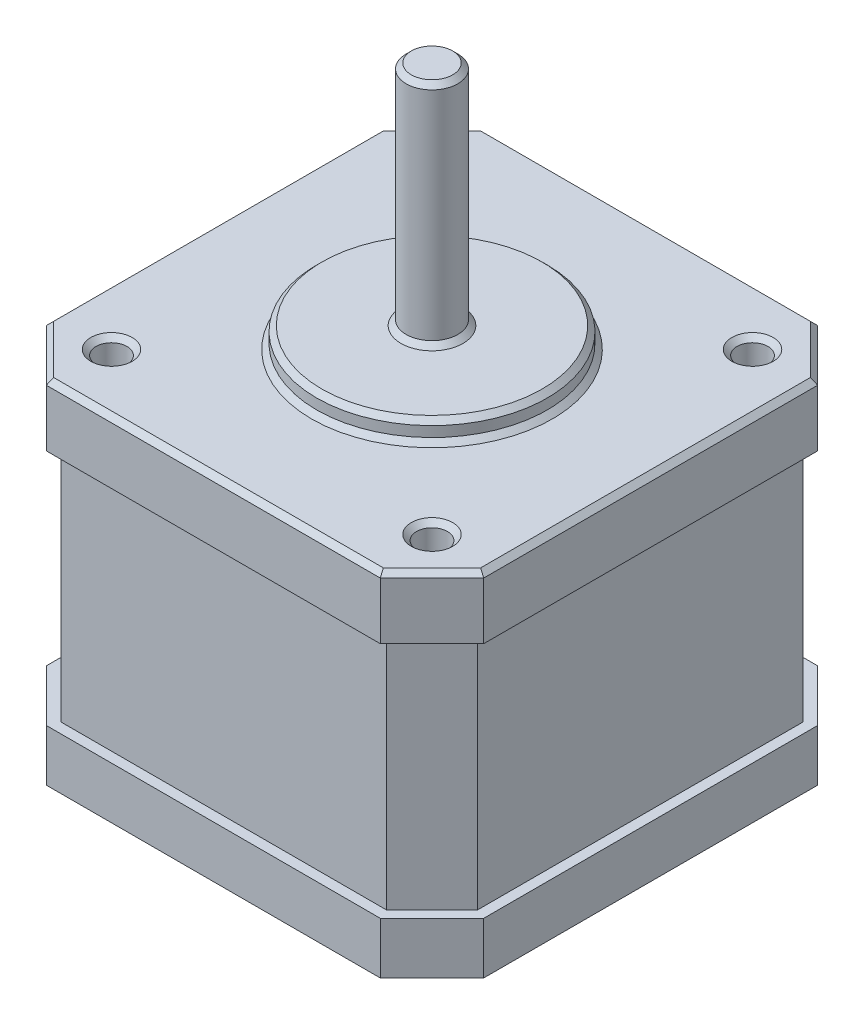
SolidWorks part; units mm, degrees
ref_plane "정면" through (0, 0, 0) normal (0, 0, 1) x (1, 0, 0)
ref_plane "윗면" through (0, 0, 0) normal (0, 1, 0) x (1, 0, 0)
ref_plane "우측면" through (0, 0, 0) normal (1, 0, 0) x (0, 0, -1)
sketch "스케치1" plane through (0, 0, 0) normal (0, 1, 0) x (1, 0, 0)
  line L0 (-21.15, 16.15) -> (-16.15, 21.15)
  line L1 (-16.15, -21.15) -> (16.15, -21.15)
  line L2 (-21.15, -16.15) -> (-21.15, 16.15)
  line L3 (-16.15, 21.15) -> (16.15, 21.15)
  line L4 (21.15, -16.15) -> (21.15, 16.15)
  line L5 (-21.15, -21.15) -> (21.15, 21.15) construction
  line L6 (-21.15, 21.15) -> (21.15, -21.15) construction
  line L7 (16.15, 21.15) -> (21.15, 16.15)
  line L8 (16.15, -21.15) -> (21.15, -16.15)
  line L9 (-21.15, -16.15) -> (-16.15, -21.15)
  line L10 (0, 15.5) -> (0, -15.5) construction
  line L11 (-15.5, -15.5) -> (15.5, -15.5) construction
  line L12 (-15.5, -15.5) -> (-15.5, 15.5) construction
  line L13 (-15.5, 15.5) -> (15.5, 15.5) construction
  line L14 (15.5, -15.5) -> (15.5, 15.5) construction
  line L15 (-15.5, -15.5) -> (15.5, 15.5) construction
  line L16 (-15.5, 15.5) -> (15.5, -15.5) construction
  line L17 (-15.5, 0) -> (15.5, 0) construction
  circle A0 centre (-15.5, 15.5) radius 1.5
  circle A1 centre (15.5, 15.5) radius 1.5
  circle A2 centre (15.5, -15.5) radius 1.5
  circle A3 centre (-15.5, -15.5) radius 1.5
  circle A4 centre (0, 0) radius 11.15
  circle A5 centre (0, 0) radius 2.5
  point P0 (0, 0)
  point P6 (18.4057, 18.4057)
  point P7 (0, 0)
  point P16 (0, 0)
  dimension "D3" = 3
  dimension "D8" = 22.3
  dimension "D9" = 5
  dimension "D1" = 42.3
  dimension "D2" = 31
extrude "보스-돌출1" add sketch "스케치1" against normal blind 34 contours L2 L9 L1 L8 L4 L7 L3 L0 A4 A1 A0 A2 A3 | A0 | A3 | A4 A5 | A5 | A2 | A1 region at (-18.227, 0, -18.227) region at (-15.5, 0, -15.5) region at (15.5, 0, -15.5) region at (15.5, 0, 15.5) region at (-15.5, 0, 15.5) region at (-10.8346, 0, 0) region at (0, 0, 0)
extrude "컷-돌출1" cut sketch "스케치1<3>" against normal blind 4.5 contours A0 | A3 | A1 | A2 region at (-15.5, 0, -15.5) region at (15.5, 0, -15.5) region at (15.5, 0, 15.5) region at (-15.5, 0, 15.5)
sketch "스케치1<3>" plane through (0, 0, 0) normal (0, 1, 0) x (1, 0, 0) same geometry as "스케치1"
extrude "보스-돌출2" add sketch "스케치1<4>" along normal blind 2 contours A4 A5 region at (-10.8346, 0, 0)
sketch "스케치1<4>" plane through (0, 0, 0) normal (0, 1, 0) x (1, 0, 0) same geometry as "스케치1"
extrude "보스-돌출3" add sketch "스케치1<5>" along normal blind 24 contours A5 region at (0, 0, 0)
sketch "스케치1<5>" plane through (0, 0, 0) normal (0, 1, 0) x (1, 0, 0) same geometry as "스케치1"
chamfer "모따기1" distance 0.5 angle 45 16 edges at (0, 24, 2.5) (0, 2, 11.15) (0, 2, 2.5) (0, 0, 11.15) (15.5, 0, 17) (-15.5, 0, 17) (-15.5, 0, -14) (-18.65, 0, -18.65) (0, 0, -21.15) (18.65, 0, -18.65) (21.15, 0, 0) (18.65, 0, 18.65) (0, 0, 21.15) (-18.65, 0, 18.65) (-21.15, 0, 0) (15.5, 0, -14)
ref_plane "평면1" through (0, -29, 0) normal (0, -1, 0) x (-1, 0, 0)
sketch "스케치2" plane through (0, -29, 0) normal (0, -1, 0) x (-1, 0, 0)
  line L16 (20.15, -15.7358) -> (20.15, 15.7358)
  line L17 (20.15, 15.7358) -> (15.7358, 20.15)
  line L18 (15.7358, 20.15) -> (-15.7358, 20.15)
  line L19 (-15.7358, 20.15) -> (-20.15, 15.7358)
  line L20 (-20.15, 15.7358) -> (-20.15, -15.7358)
  line L21 (-20.15, -15.7358) -> (-15.7358, -20.15)
  line L22 (-15.7358, -20.15) -> (15.7358, -20.15)
  line L23 (15.7358, -20.15) -> (20.15, -15.7358)
  line L24 (20.15, -15.7358) -> (20.15, 15.7358)
  line L25 (20.15, 15.7358) -> (15.7358, 20.15)
  line L26 (15.7358, 20.15) -> (-15.7358, 20.15)
  line L27 (-15.7358, 20.15) -> (-20.15, 15.7358)
  line L28 (-20.15, 15.7358) -> (-20.15, -15.7358)
  line L29 (-20.15, -15.7358) -> (-15.7358, -20.15)
  line L30 (-15.7358, -20.15) -> (15.7358, -20.15)
  line L31 (15.7358, -20.15) -> (20.15, -15.7358)
  line L32 (21.15, -16.15) -> (21.15, 16.15)
  line L33 (21.15, 16.15) -> (16.15, 21.15)
  line L34 (16.15, 21.15) -> (-16.15, 21.15)
  line L35 (-16.15, 21.15) -> (-21.15, 16.15)
  line L36 (-21.15, 16.15) -> (-21.15, -16.15)
  line L37 (-21.15, -16.15) -> (-16.15, -21.15)
  line L38 (-16.15, -21.15) -> (16.15, -21.15)
  line L39 (16.15, -21.15) -> (21.15, -16.15)
  line L40 (21.15, -16.15) -> (21.15, 16.15)
  line L41 (21.15, 16.15) -> (16.15, 21.15)
  line L42 (16.15, 21.15) -> (-16.15, 21.15)
  line L43 (-16.15, 21.15) -> (-21.15, 16.15)
  line L44 (-21.15, 16.15) -> (-21.15, -16.15)
  line L45 (-21.15, -16.15) -> (-16.15, -21.15)
  line L46 (-16.15, -21.15) -> (16.15, -21.15)
  line L47 (16.15, -21.15) -> (21.15, -16.15)
  dimension "D1" = 1
  dimension "D2" = 0
extrude "컷-돌출2" cut sketch "스케치2" against normal blind 23
